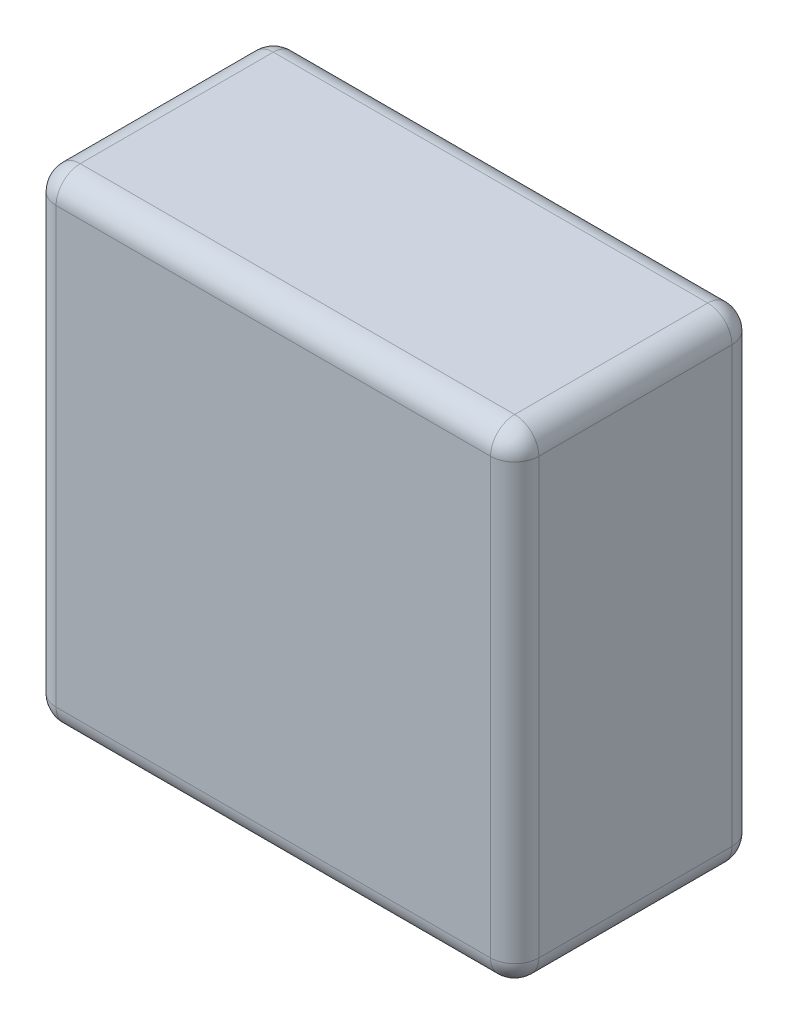
SolidWorks part; units mm, degrees
ref_plane "Plan de face" through (0, 0, 0) normal (0, 0, 1) x (1, 0, 0)
ref_plane "Plan de dessus" through (0, 0, 0) normal (0, 1, 0) x (1, 0, 0)
ref_plane "Plan de droite" through (0, 0, 0) normal (1, 0, 0) x (0, 0, -1)
sketch "Esquisse1" plane through (0, 0, 0) normal (0, 0, 1) x (1, 0, 0)
  line L1 (0, 0) -> (10, 0)
  line L2 (0, 0) -> (0, -10)
  line L3 (0, -10) -> (10, -10)
  line L4 (10, 0) -> (10, -10)
  dimension "D1" = 10
  dimension "D2" = 10
extrude "Boss.-Extru.1" add sketch "Esquisse1" along normal blind 5
fillet "Congé1" radius 0.5 12 edges at (0, 0, 2.5) (0, -10, 2.5) (10, -10, 2.5) (10, 0, 2.5) (5, -10, 0) (10, -5, 0) (5, 0, 0) (0, -5, 0) (5, 0, 5) (10, -5, 5) (5, -10, 5) (0, -5, 5)
